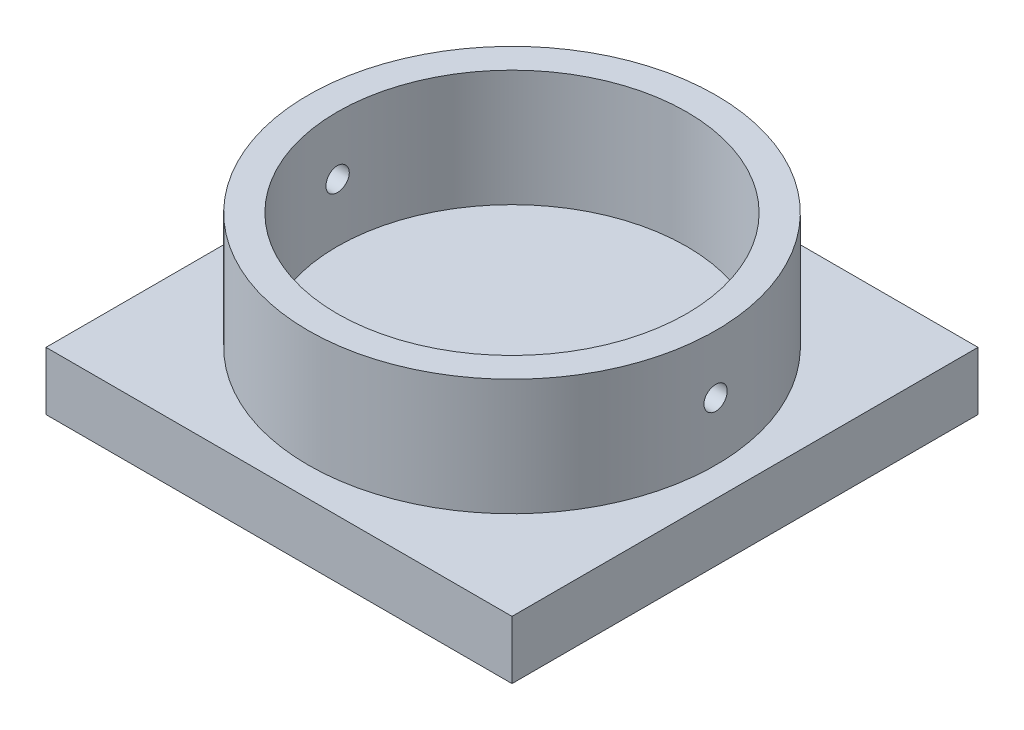
SolidWorks part; units mm, degrees
ref_plane "Front Plane" through (0, 0, 0) normal (0, 0, 1) x (1, 0, 0)
ref_plane "Top Plane" through (0, 0, 0) normal (0, 1, 0) x (1, 0, 0)
ref_plane "Right Plane" through (0, 0, 0) normal (1, 0, 0) x (0, 0, -1)
sketch "Sketch1" plane through (0, 0, 0) normal (0, 1, 0) x (1, 0, 0)
  line L1 (0, 0) -> (101.6, 0)
  line L2 (0, 0) -> (0, 101.6)
  line L3 (0, 101.6) -> (101.6, 101.6)
  line L4 (101.6, 0) -> (101.6, 101.6)
  dimension "D1" = 101.6
  dimension "D2" = 101.6
extrude "Boss-Extrude1" add sketch "Sketch1" along normal blind 12.7
sketch "Sketch2" plane through (0, 12.7, 0) normal (0, 1, 0) x (1, 0, 0)
  line L0 (101.6, 101.6) -> (0, 101.6) construction
  line L1 (0, 101.6) -> (0, 0) construction
  circle A0 centre (50.8, 50.8) radius 38.1
  circle A1 centre (50.8, 50.8) radius 44.45
  point P5 (50.8, 101.6)
  point P8 (0, 50.8)
  dimension "D1" = 76.2
  dimension "D2" = 6.35
extrude "Boss-Extrude2" add sketch "Sketch2" along normal blind 25.4
sketch "Sketch3" plane through (101.6, 0, 0) normal (1, 0, 0) x (0, 0, -1)
  line L0 (0, 12.7) -> (101.6, 12.7) construction
  line L3 (95.25, 38.1) -> (6.35, 38.1) construction
  circle A0 centre (50.8, 25.4) radius 2.54
  point P2 (0, 0)
  point P3 (68.7788, 27.5947)
  point P6 (50.8, 12.7)
  dimension "D1" = 5.08
  dimension "D2" = 12.7
extrude "Cut-Extrude1" cut sketch "Sketch3" against normal up to surface (101.6 mm away) up to face at (0, 6.35, -50.8)
